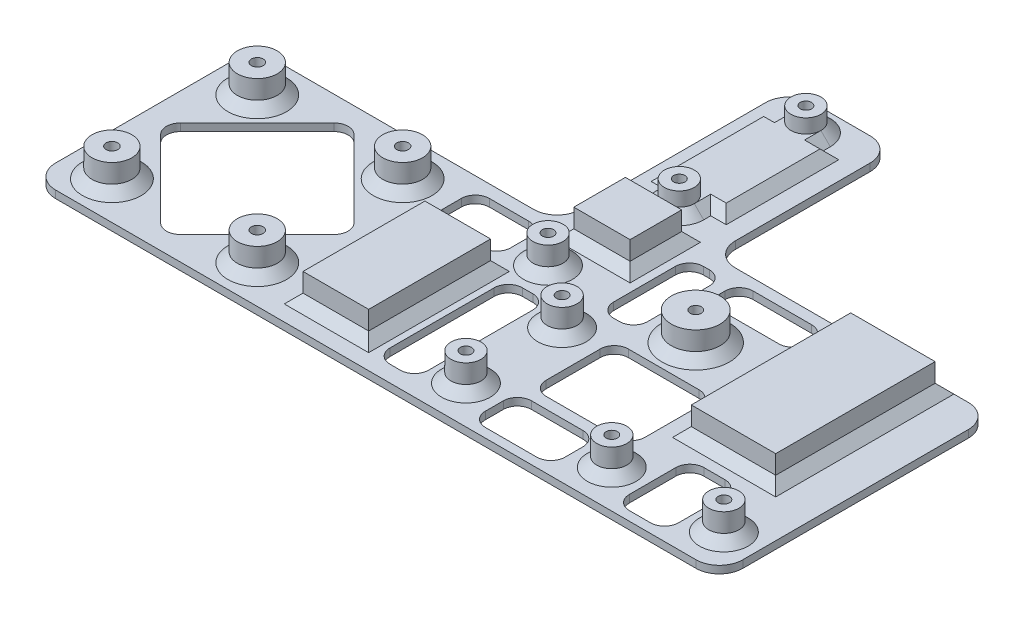
SolidWorks part; units mm, degrees
ref_plane "Front Plane" through (0, 0, 0) normal (0, 0, 1) x (1, 0, 0)
ref_plane "Top Plane" through (0, 0, 0) normal (0, 1, 0) x (1, 0, 0)
ref_plane "Right Plane" through (0, 0, 0) normal (1, 0, 0) x (0, 0, -1)
sketch "Sketch2" plane through (0, 0, 0) normal (0, 1, 0) x (1, 0, 0)
  line L1 (-228.2596, -185.0339) -> (155.3205, -185.0339)
  line L2 (-228.2596, -185.0339) -> (-228.2596, 209.7153)
  line L3 (-228.2596, 209.7153) -> (155.3205, 209.7153)
  line L4 (155.3205, -185.0339) -> (155.3205, 209.7153)
  line L5 (-228.2596, -185.0339) -> (155.3205, 209.7153) construction
  line L6 (-228.2596, 209.7153) -> (155.3205, -185.0339) construction
  point P4 (-36.4696, 12.3407)
extrude "Boss-Extrude1" add sketch "Sketch2" against normal blind 10
sketch "Sketch1" plane through (0, 0, 0) normal (0, 1, 0) x (1, 0, 0)
  line L0 (-23.9, 0) -> (0, 0) construction
  line L1 (-23.9, 1.2) -> (-23.9, 3.2) construction
  line L4 (0, 3.2) -> (0, 1.2) construction
  circle A0 centre (-23.9, 0) radius 1.2
  circle A1 centre (0, 0) radius 1.2
  circle A2 centre (-23.9, 0) radius 3.2
  circle A3 centre (0, 0) radius 3.2
  dimension "D2" = 2.4
  dimension "D3" = 2
  dimension "D1" = 23.9
extrude "Boss-Extrude2" add sketch "Sketch1" along normal blind 6
sketch "Sketch4" plane through (0, 0, 0) normal (0, 1, 0) x (1, 0, 0)
  line L0 (-55, 0) -> (-55, 20.5) construction
  line L1 (-53.8, 20.5) -> (-51.8, 20.5) construction
  line L4 (-51.8, 0) -> (-53.8, 0) construction
  circle A0 centre (-55, 0) radius 1.2
  circle A1 centre (-55, 20.5) radius 1.2
  circle A2 centre (-55, 20.5) radius 3.2
  circle A3 centre (-55, 0) radius 3.2
  point P10 (0, 0)
  dimension "D1" = 2.4
  dimension "D2" = 20.5
  dimension "D3" = 2
  dimension "D4" = 55
extrude "Boss-Extrude3" add sketch "Sketch4" along normal blind 6
sketch "Sketch5" plane through (0, 0, 0) normal (0, 1, 0) x (1, 0, 0)
  circle A0 centre (-68, 30.5) radius 1.2
  circle A1 centre (-55, 20.5) radius 1.2 construction
  circle A2 centre (-55, 20.5) radius 1.2 construction
  circle A3 centre (-68, 30.5) radius 3.2
  dimension "D1" = 2.4
  dimension "D4" = 2
  dimension "D2" = 13
  dimension "D3" = 10
extrude "Boss-Extrude4" add sketch "Sketch5" along normal blind 6
sketch "Sketch6" plane through (0, 0, 0) normal (0, 1, 0) x (1, 0, 0)
  line L0 (-65, 82.5) -> (-65, 55.5) construction
  line L2 (-58.5, 79) -> (-70.5, 79)
  line L3 (-58.5, 79) -> (-58.5, 59)
  line L4 (-58.5, 59) -> (-70.5, 59)
  line L5 (-70.5, 79) -> (-70.5, 59)
  line L6 (-58.5, 79) -> (-70.5, 59) construction
  line L7 (-58.5, 59) -> (-70.5, 79) construction
  circle A0 centre (-65, 55.5) radius 1.2 construction
  circle A1 centre (-68, 30.5) radius 1.2 construction
  circle A2 centre (-68, 30.5) radius 1.2 construction
  circle A4 centre (-65, 82.5) radius 1.2 construction
  point P11 (-64.5, 69)
  point P12 (-65, 69)
  dimension "D2" = 2.4
  dimension "D3" = 27
  dimension "D1" = 25
  dimension "D4" = 3
  dimension "D5" = 20
  dimension "D6" = 12
  dimension "D7" = 0.5
extrude "Boss-Extrude5" add sketch "Sketch6" along normal blind 2
sketch "Sketch7" plane through (0, 0, 0) normal (0, 1, 0) x (1, 0, 0)
  line L0 (-63.8, 82.5) -> (-61.8, 82.5) construction
  line L1 (-61.8, 55.5) -> (-63.8, 55.5) construction
  line L2 (-68.2, 55.5) -> (-68.2, 59)
  line L3 (-70.5, 59) -> (-58.5, 59) construction
  line L4 (-68.2, 59) -> (-61.8, 59)
  line L5 (-70.5, 59) -> (-58.5, 59) construction
  line L6 (-61.8, 59) -> (-61.8, 55.5)
  line L7 (-68.2, 79) -> (-68.2, 82.5)
  line L8 (-58.5, 79) -> (-70.5, 79) construction
  line L9 (-61.8, 82.5) -> (-61.8, 79)
  line L10 (-58.5, 79) -> (-70.5, 79) construction
  line L11 (-61.8, 79) -> (-68.2, 79)
  circle A0 centre (-65, 82.5) radius 1.2 construction
  circle A1 centre (-65, 55.5) radius 1.2 construction
  circle A2 centre (-65, 82.5) radius 1.2
  circle A3 centre (-65, 55.5) radius 1.2
  circle A4 centre (-65, 82.5) radius 3.2 construction
  circle A5 centre (-65, 55.5) radius 3.2 construction
  arc A6 (-61.8, 55.5) -> (-68.2, 55.5) centre (-65, 55.5) cw
  arc A7 (-68.2, 82.5) -> (-61.8, 82.5) centre (-65, 82.5) cw
  dimension "D1" = 2
extrude "Boss-Extrude6" add sketch "Sketch7" along normal blind 2
sketch "Sketch8" plane through (0, 2, 0) normal (0, 1, 0) x (1, 0, 0)
  circle A0 centre (-65, 55.5) radius 3.2
  circle A1 centre (-65, 82.5) radius 3.2
  circle A2 centre (-65, 82.5) radius 1.2
  circle A3 centre (-65, 55.5) radius 1.2
extrude "Boss-Extrude7" add sketch "Sketch8" along normal blind 3
sketch "Sketch9" plane through (0, 0, 0) normal (0, 1, 0) x (1, 0, 0)
  circle A0 centre (-38, 32) radius 1.2
  circle A1 centre (-38, 32) radius 5.2
  dimension "D1" = 4
  dimension "D2" = 2.4
  dimension "D3" = 38
  dimension "D4" = 32
extrude "Boss-Extrude8" add sketch "Sketch9" along normal blind 6
sketch "Sketch10" plane through (0, 0, 0) normal (0, 1, 0) x (1, 0, 0)
  line L1 (-130.5, 0) -> (-99.5, 0) construction
  line L2 (-130.5, 0) -> (-130.5, 31) construction
  line L3 (-130.5, 31) -> (-99.5, 31) construction
  line L4 (-99.5, 0) -> (-99.5, 31) construction
  line L5 (-130.5, 0) -> (-99.5, 31) construction
  line L6 (-130.5, 31) -> (-99.5, 0) construction
  circle A0 centre (-130.5, 31) radius 1.25
  circle A1 centre (-99.5, 31) radius 1.25
  circle A2 centre (-99.5, 0) radius 1.25
  circle A3 centre (-130.5, 0) radius 1.25
  circle A4 centre (-130.5, 31) radius 4.25
  circle A5 centre (-99.5, 31) radius 4.25
  circle A6 centre (-99.5, 0) radius 4.25
  circle A7 centre (-130.5, 0) radius 4.25
  point P4 (-115, 15.5)
  point P13 (-125.6254, 11.7694)
  point P14 (-100.2935, 25.077)
  point P16 (-103.7943, -1.4293)
  dimension "D1" = 3
  dimension "D2" = 2.5
  dimension "D3" = 31
  dimension "D4" = 115
extrude "Boss-Extrude9" add sketch "Sketch10" along normal blind 6
chamfer "Chamfer1" distance 2 angle 45 22 edges at (0, 0, -3.2) (-23.9, 0, -3.2) (-55, 0, -23.7) (-55, 0, -3.2) (-68, 0, -33.7) (-99.5, 0, -35.25) (-130.5, 0, -35.25) (-68.2, 0, -80.75) (-65, 0, -85.7) (-61.8, 0, -80.75) (-60.15, 0, -79) (-58.5, 0, -69) (-60.15, 0, -59) (-61.8, 0, -57.25) (-69.35, 0, -79) (-70.5, 0, -69) (-69.35, 0, -59) (-68.2, 0, -57.25) (-65, 0, -52.3) (-130.5, 0, -4.25) (-99.5, 0, -4.25) (-38, 0, -37.2)
sketch "Sketch12" plane through (0, -10, 0) normal (0, -1, 0) x (1, 0, 0)
  line L4 (-228.2596, 185.0339) -> (-228.2596, -209.7153)
  line L5 (-228.2596, 185.0339) -> (-228.2596, -209.7153)
  line L6 (-228.2596, -209.7153) -> (155.3205, -209.7153)
  line L7 (-228.2596, -209.7153) -> (155.3205, -209.7153)
  line L12 (155.3205, -209.7153) -> (155.3205, 185.0339)
  line L13 (155.3205, -209.7153) -> (155.3205, 185.0339)
  line L14 (155.3205, 185.0339) -> (-228.2596, 185.0339)
  line L15 (155.3205, 185.0339) -> (-228.2596, 185.0339)
  dimension "D1" = 0
extrude "Cut-Extrude4" cut sketch "Sketch12" against normal blind 8.4
sketch "Sketch14" plane through (0, 0, 0) normal (0, 1, 0) x (1, 0, 0)
  line L0 (-23.9, 0) -> (0, 0) construction
  line L1 (-20.95, 48) -> (-2.95, 48)
  line L2 (-20.95, 48) -> (-20.95, 14)
  line L3 (-20.95, 14) -> (-2.95, 14)
  line L4 (-2.95, 48) -> (-2.95, 14)
  line L5 (-20.95, 48) -> (-2.95, 14) construction
  line L6 (-20.95, 14) -> (-2.95, 48) construction
  line L7 (-55, 20.5) -> (-55, 0) construction
  line L9 (-73, 23.25) -> (-87, 23.25)
  line L10 (-73, 23.25) -> (-73, -2.75)
  line L11 (-73, -2.75) -> (-87, -2.75)
  line L12 (-87, 23.25) -> (-87, -2.75)
  line L13 (-73, 23.25) -> (-87, -2.75) construction
  line L14 (-73, -2.75) -> (-87, 23.25) construction
  line L15 (-70, 38) -> (-58, 38)
  line L16 (-70, 38) -> (-70, 49)
  line L17 (-70, 49) -> (-58, 49)
  line L18 (-58, 38) -> (-58, 49)
  line L19 (-70, 38) -> (-58, 49) construction
  line L20 (-70, 49) -> (-58, 38) construction
  circle A0 centre (-68, 30.5) radius 1.2 construction
  circle A1 centre (-68, 30.5) radius 1.2 construction
  point P4 (-11.95, 31)
  point P9 (-11.95, 0)
  point P18 (-80, 10.25)
  point P19 (-57.51, 49.2716)
  point P20 (-55, 10.25)
  point P21 (-88.9897, 18.4932)
  point P22 (-73.4148, 23.25)
  point P27 (-64, 43.5)
  point P29 (0, 0)
  point P30 (-69.3672, 37.732)
  point P31 (-22.1079, 48.5)
  point P32 (-21.0187, 14.7134)
  point P33 (-2.8459, 48.5)
  point P37 (-63.2118, 43.5)
  dimension "D1" = 26
  dimension "D2" = 14
  dimension "D3" = 32
  dimension "D4" = 34
  dimension "D5" = 18
  dimension "D6" = 14
  dimension "D7" = 7.5
  dimension "D8" = 12
  dimension "D9" = 11
  dimension "D10" = 10
extrude "Boss-Extrude10" add sketch "Sketch14" along normal blind 6
chamfer "Chamfer2" distance 2 angle 45 12 edges at (-11.95, 0, -14) (-2.95, 0, -31) (-11.95, 0, -48) (-20.95, 0, -31) (-80, 0, -23.25) (-87, 0, -10.25) (-80, 0, 2.75) (-73, 0, -10.25) (-64, 0, -38) (-58, 0, -43.5) (-64, 0, -49) (-70, 0, -43.5)
sketch "Sketch15" plane through (0, 0, 0) normal (0, 1, 0) x (1, 0, 0)
  line L0 (7.1363, -8.087) -> (7.1363, 50)
  line L1 (7.1363, 50) -> (-52.5556, 50)
  line L2 (-52.5556, 50) -> (-52.5556, 88.7646)
  line L3 (-52.5556, 88.7646) -> (-74.8607, 88.7646)
  line L4 (-74.8607, 88.7646) -> (-74.8607, 39.2991)
  line L5 (-74.8607, 39.2991) -> (-139.4117, 39.2991)
  line L6 (-139.4117, 39.2991) -> (-139.4117, -8.087)
  line L7 (-139.4117, -8.087) -> (7.1363, -8.087)
  line L8 (-22.95, 50) -> (-0.95, 50) construction
  line L13 (-228.2596, 209.7153) -> (-228.2596, -185.0339)
  line L14 (-228.2596, -185.0339) -> (155.3205, -185.0339)
  line L15 (155.3205, -185.0339) -> (155.3205, 209.7153)
  line L16 (155.3205, 209.7153) -> (-228.2596, 209.7153)
  line L17 (-228.2596, 209.7153) -> (-228.2596, -185.0339)
  line L18 (-228.2596, -185.0339) -> (155.3205, -185.0339)
  line L19 (155.3205, -185.0339) -> (155.3205, 209.7153)
  line L20 (155.3205, 209.7153) -> (-228.2596, 209.7153)
  dimension "D1" = 0
extrude "Cut-Extrude5" cut sketch "Sketch15" against normal through all
fillet "Fillet1" radius 5 8 edges at (-139.4117, -0.8, 8.087) (7.1363, -0.8, 8.087) (-52.5556, -0.8, -50) (-74.8607, -0.8, -39.2991) (-139.4117, -0.8, -39.2991) (-52.5556, -0.8, -88.7646) (7.1363, -0.8, -50) (-74.8607, -0.8, -88.7646)
sketch "Sketch16" plane through (0, 0, 0) normal (0, 1, 0) x (1, 0, 0)
  line L0 (-115, 36.1072) -> (-135.6072, 15.5)
  line L1 (-115, 36.1072) -> (-94.3928, 15.5)
  line L2 (-135.6072, 15.5) -> (-115, -5.1072)
  line L3 (-94.3928, 15.5) -> (-115, -5.1072)
  line L4 (-130.5, 31) -> (-99.5, 31) construction
  line L5 (-25.901, 23.6276) -> (-46.9928, 23.6276)
  line L6 (-25.901, 23.6276) -> (-25.901, 6.1052)
  line L7 (-25.901, 6.1052) -> (-46.9928, 6.1052)
  line L8 (-46.9928, 23.6276) -> (-46.9928, 6.1052)
  line L9 (-25.901, 23.6276) -> (-46.9928, 6.1052) construction
  line L10 (-25.901, 6.1052) -> (-46.9928, 23.6276) construction
  line L11 (-99.5, 31) -> (-99.5, 0) construction
  line L12 (-115, 36.1072) -> (-115, -5.1072) construction
  line L14 (-46.9928, 27.7378) -> (-54.2397, 27.7378)
  line L15 (-46.9928, 27.7378) -> (-46.9928, 46.8827)
  line L16 (-46.9928, 46.8827) -> (-54.2397, 46.8827)
  line L17 (-54.2397, 27.7378) -> (-54.2397, 46.8827)
  line L18 (-46.9928, 27.7378) -> (-54.2397, 46.8827) construction
  line L19 (-46.9928, 46.8827) -> (-54.2397, 27.7378) construction
  line L20 (-17.0316, 9.7827) -> (-6.5398, 9.7827)
  line L21 (-17.0316, 9.7827) -> (-17.0316, -6.1173)
  line L22 (-17.0316, -6.1173) -> (-6.5398, -6.1173)
  line L23 (-6.5398, 9.7827) -> (-6.5398, -6.1173)
  line L24 (-17.0316, 9.7827) -> (-6.5398, -6.1173) construction
  line L25 (-17.0316, -6.1173) -> (-6.5398, 9.7827) construction
  line L26 (-30.7683, -6.1173) -> (-47.75, -6.1173)
  line L27 (-30.7683, -6.1173) -> (-30.7683, 3.7256)
  line L28 (-30.7683, 3.7256) -> (-47.75, 3.7256)
  line L29 (-47.75, -6.1173) -> (-47.75, 3.7256)
  line L30 (-30.7683, -6.1173) -> (-47.75, 3.7256) construction
  line L31 (-30.7683, 3.7256) -> (-47.75, -6.1173) construction
  line L32 (-61.3785, -4.6072) -> (-69.5989, -4.6072)
  line L33 (-61.3785, -4.6072) -> (-61.3785, 23.6276)
  line L34 (-61.3785, 23.6276) -> (-69.5989, 23.6276)
  line L35 (-69.5989, -4.6072) -> (-69.5989, 23.6276)
  line L36 (-61.3785, -4.6072) -> (-69.5989, 23.6276) construction
  line L37 (-61.3785, 23.6276) -> (-69.5989, -4.6072) construction
  line L38 (-75.2234, 26.7643) -> (-89.6091, 26.7643)
  line L39 (-75.2234, 26.7643) -> (-75.2234, 36.6072)
  line L40 (-75.2234, 36.6072) -> (-89.6091, 36.6072)
  line L41 (-89.6091, 26.7643) -> (-89.6091, 36.6072)
  line L42 (-75.2234, 26.7643) -> (-89.6091, 36.6072) construction
  line L43 (-75.2234, 36.6072) -> (-89.6091, 26.7643) construction
  line L44 (-44.3969, 40.6092) -> (-25.901, 40.6092)
  line L45 (-44.3969, 40.6092) -> (-44.3969, 47.6398)
  line L46 (-44.3969, 47.6398) -> (-25.901, 47.6398)
  line L47 (-25.901, 40.6092) -> (-25.901, 47.6398)
  line L48 (-44.3969, 40.6092) -> (-25.901, 47.6398) construction
  line L49 (-44.3969, 47.6398) -> (-25.901, 40.6092) construction
  point P8 (-36.4469, 14.8664)
  point P9 (-115, 15.5)
  point P16 (-99.5, 15.5)
  point P17 (-115, 31)
  point P26 (-50.6163, 37.3102)
  point P27 (-11.7857, 1.8327)
  point P32 (-39.2591, -1.1959)
  point P37 (-65.4887, 9.5102)
  point P42 (-82.4162, 31.6857)
  point P47 (-35.1489, 44.1245)
  dimension "D1" = 45
extrude "Cut-Extrude6" cut sketch "Sketch16" against normal through all
fillet "Fillet2" radius 3 32 edges at (-75.2234, -0.8, -26.7643) (-61.3785, -0.8, 4.6072) (-46.9928, -0.8, -27.7378) (-25.901, -0.8, -6.1052) (-25.901, -0.8, -40.6092) (-30.7683, -0.8, 6.1173) (-6.5398, -0.8, 6.1173) (-115, -0.8, 5.1072) (-89.6091, -0.8, -26.7643) (-69.5989, -0.8, 4.6072) (-54.2397, -0.8, -27.7378) (-44.3969, -0.8, -40.6092) (-46.9928, -0.8, -6.1052) (-47.75, -0.8, 6.1173) (-17.0316, -0.8, 6.1173) (-135.6072, -0.8, -15.5) (-47.75, -0.8, -3.7256) (-17.0316, -0.8, -9.7827) (-46.9928, -0.8, -23.6276) (-44.3969, -0.8, -47.6398) (-54.2397, -0.8, -46.8827) (-89.6091, -0.8, -36.6072) (-69.5989, -0.8, -23.6276) (-115, -0.8, -36.1072) (-94.3928, -0.8, -15.5) (-75.2234, -0.8, -36.6072) (-61.3785, -0.8, -23.6276) (-30.7683, -0.8, -3.7256) (-6.5398, -0.8, -9.7827) (-25.901, -0.8, -23.6276) (-46.9928, -0.8, -46.8827) (-25.901, -0.8, -47.6398)
